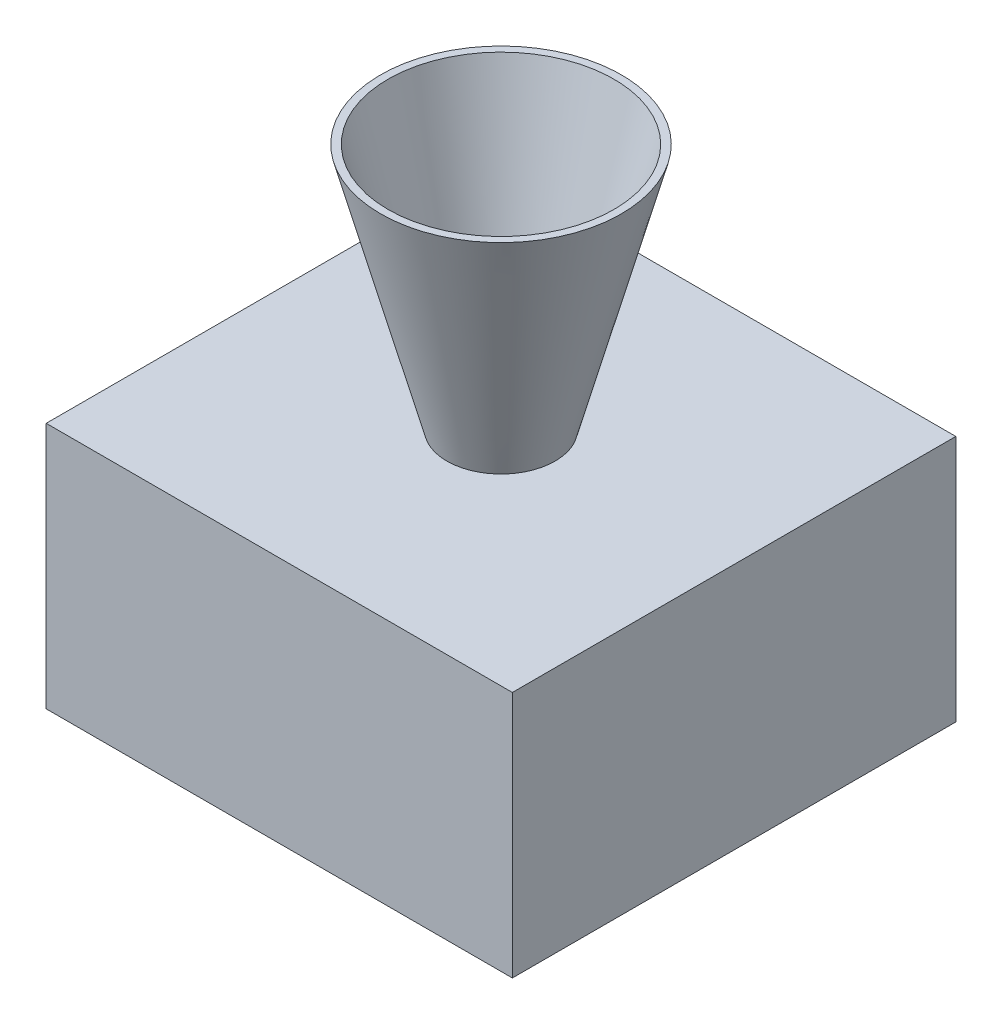
SolidWorks part; units mm, degrees
ref_plane "Front Plane" through (0, 0, 0) normal (0, 0, 1) x (1, 0, 0)
ref_plane "Top Plane" through (0, 0, 0) normal (0, 1, 0) x (1, 0, 0)
ref_plane "Right Plane" through (0, 0, 0) normal (1, 0, 0) x (0, 0, -1)
sketch "Sketch1" plane through (0, 0, 0) normal (0, 1, 0) x (1, 0, 0)
  line L1 (-82, 78) -> (82, 78)
  line L2 (-82, 78) -> (-82, -78)
  line L3 (-82, -78) -> (82, -78)
  line L4 (82, 78) -> (82, -78)
  line L5 (-82, 78) -> (82, -78) construction
  line L6 (-82, -78) -> (82, 78) construction
  point P0 (0, 0)
  dimension "D1" = 164
  dimension "D2" = 156
extrude "Boss-Extrude2" add sketch "Sketch1" along normal blind 87 contours L1 L4 L3 L2
sketch "Sketch2" plane through (0, 87, 0) normal (0, 1, 0) x (1, 0, 0)
  circle A0 centre (0, 0) radius 19.05
extrude "Boss-Extrude3" add sketch "Sketch2" along normal blind 87 draft 15 contours A0 draft outward yes
shell "Shell1" thickness 2.54 removed face at (0, 174, 42.3616)
